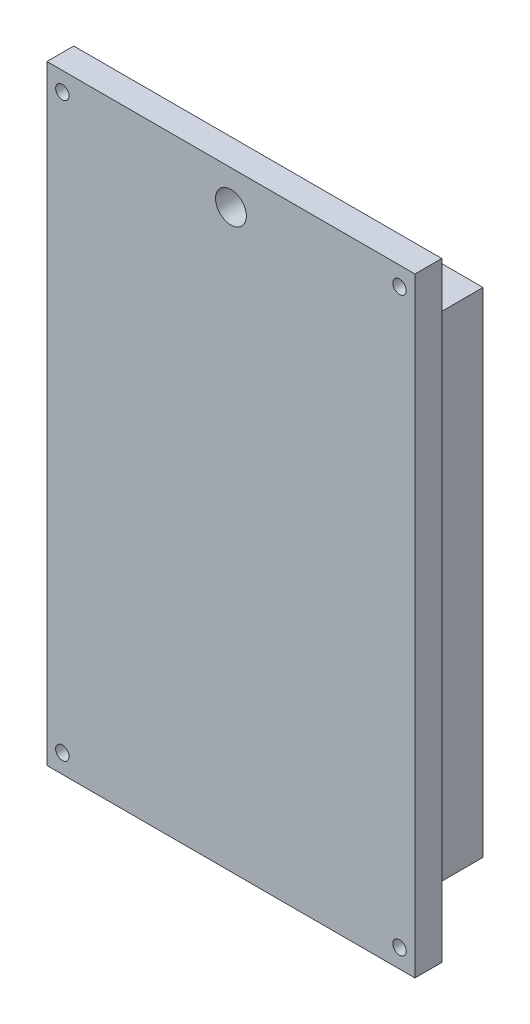
SolidWorks part; units mm, degrees
ref_plane "Front" through (0, 0, 0) normal (0, 0, 1) x (1, 0, 0)
ref_plane "Top" through (0, 0, 0) normal (0, 1, 0) x (1, 0, 0)
ref_plane "Right" through (0, 0, 0) normal (1, 0, 0) x (0, 0, -1)
sketch "arduinoOutline" plane through (0, 0, 0) normal (0, 0, 1) x (1, 0, 0)
  line L0 (0, 32.73) -> (2.54, 35.27) construction
  line L2 (0, 0) -> (0, 32.73) construction
  line L5 (2.54, 35.27) -> (2.54, 36.81) construction
  line L6 (3.54, 37.81) -> (67.6, 37.81) construction
  line L7 (68.6, 36.81) -> (68.6, -14.59) construction
  line L8 (67.6, -15.59) -> (4.06, -15.59) construction
  line L9 (4.06, -15.59) -> (2.54, -14.07) construction
  line L10 (2.54, -14.07) -> (2.54, -2.54) construction
  line L11 (2.54, -2.54) -> (0, 0) construction
  arc A0 (2.54, 36.81) -> (3.54, 37.81) centre (3.54, 36.81) cw construction
  arc A1 (68.6, -14.59) -> (67.6, -15.59) centre (67.6, -14.59) cw construction
  arc A2 (67.6, 37.81) -> (68.6, 36.81) centre (67.6, 36.81) cw construction
  point P8 (2.54, 37.81)
  point P13 (68.6, -15.59)
  point P16 (68.6, 37.81)
  dimension "D6" = 1
  dimension "D9" = 1
  dimension "D10" = 1
  dimension "D1" = 32.73
  dimension "D2" = 135
  dimension "D3" = 3.5921
  dimension "D4" = 2.54
  dimension "D5" = 66.06
  dimension "D7" = 53.4
  dimension "D8" = 64.54
  dimension "D11" = 135
  dimension "D12" = 2.1496
  dimension "D13" = 11.53
  dimension "D14" = 135
  dimension "D15" = 3.5921
sketch "arduinoMountingHolesSketch" plane through (0, 0, 0) normal (0, 0, 1) x (1, 0, 0)
  line L0 (0, 0) -> (0, 32.73) construction
  line L1 (67.6, -15.59) -> (4.06, -15.59) construction
  line L2 (3.54, 37.81) -> (67.6, 37.81) construction
  line L3 (68.6, 36.81) -> (68.6, -14.59) construction
  circle A0 centre (2.54, 2.28) radius 1.25
  circle A1 centre (2.54, 30.45) radius 1.25
  circle A2 centre (54.6, 35.27) radius 1.25
  circle A3 centre (53.35, -13.05) radius 1.25
  dimension "D9" = 2.5
  dimension "D1" = 2.54
  dimension "D2" = 17.87
  dimension "D3" = 2.54
  dimension "D4" = 7.36
  dimension "D5" = 2.54
  dimension "D6" = 14
  dimension "D7" = 2.54
  dimension "D8" = 15.25
sketch "9VbatteryMountingHolesSketch" plane through (0, 0, 0) normal (0, 0, 1) x (1, 0, 0)
  line L0 (0, 16.365) -> (68.6, 16.365) construction
  line L1 (4.875, 40.31) -> (63.725, 40.31) construction
  line L2 (4.875, 40.31) -> (4.875, 88.56) construction
  line L3 (4.875, 88.56) -> (63.725, 88.56) construction
  line L4 (63.725, 40.31) -> (63.725, 88.56) construction
  line L5 (0, 0) -> (0, 32.73) construction
  line L6 (68.6, 36.81) -> (68.6, -14.59) construction
  line L7 (34.3, 40.31) -> (34.3, 88.56) construction
  line L8 (4.875, 64.435) -> (63.725, 64.435) construction
  line L10 (3.54, 37.81) -> (67.6, 37.81) construction
  circle A0 centre (8.625, 86.06) radius 1.25
  circle A1 centre (59.975, 86.06) radius 1.25
  circle A2 centre (8.625, 42.81) radius 1.25
  circle A3 centre (59.975, 42.81) radius 1.25
  point P4 (34.3, 16.365)
  point P5 (34.3, 88.56)
  dimension "D3" = 2.5
  dimension "D1" = 48.25
  dimension "D2" = 58.85
  dimension "D4" = 2.5
  dimension "D5" = 3.75
  dimension "D6" = 2.5
sketch "legBracketMountingHolesSketch" plane through (0, 0, 0) normal (0, 0, 1) x (1, 0, 0)
  line L0 (34.3, 91.06) -> (34.3, 98.06) construction
  line L1 (24.1051, 98.06) -> (44.4949, 98.06) construction
  line L2 (24.1051, 98.06) -> (24.1051, 91.06) construction
  line L3 (24.1051, 91.06) -> (44.4949, 91.06) construction
  line L4 (44.4949, 98.06) -> (44.4949, 91.06) construction
  circle A0 centre (29.2026, 94.56) radius 2
  circle A1 centre (39.3974, 94.56) radius 2
  point P4 (24.1051, 94.56)
  point P5 (34.3, 98.06)
  dimension "D4" = 4
  dimension "D1" = 7
  dimension "D2" = 20.3898
  dimension "D3" = 2.5
  dimension "D5" = 5.0974
sketch "backsideMountingHolesSketch" plane through (0, 0, 0) normal (0, 0, 1) x (1, 0, 0)
  line L0 (0, 41.235) -> (68.6, 41.235) construction
  line L9 (0, 0) -> (0, 32.73) construction
  line L10 (34.3, 40.31) -> (34.3, 88.56) construction
  line L11 (68.6, 36.81) -> (68.6, -14.59) construction
  line L12 (24.1051, 98.06) -> (44.4949, 98.06) construction
  line L13 (4.875, 88.56) -> (63.725, 88.56) construction
  line L14 (4.875, 40.31) -> (4.875, 88.56) construction
  circle A1 centre (2.875, 94.56) radius 1.25
  circle A5 centre (65.725, 94.56) radius 1.25
  circle A6 centre (65.725, -12.09) radius 1.25
  circle A7 centre (2.875, -12.09) radius 1.25
  dimension "D1" = 2.5
  dimension "D2" = 56.825
  dimension "D3" = 6
  dimension "D4" = 2
sketch "Sketch1" plane through (0, 0, 0) normal (0, 0, 1) x (1, 0, 0)
  line L0 (67.6, -15.59) -> (4.06, -15.59) construction
  line L1 (0, 98.06) -> (68.6, 98.06)
  line L2 (0, 98.06) -> (0, -15.59)
  line L3 (0, -15.59) -> (68.6, -15.59)
  line L4 (68.6, 98.06) -> (68.6, -15.59)
  line L5 (0, 0) -> (0, 32.73) construction
  line L6 (68.6, 36.81) -> (68.6, -14.59) construction
  line L9 (24.1051, 98.06) -> (44.4949, 98.06) construction
extrude "bracketBase" add sketch "Sketch1" along normal blind 5
extrude "arduinoMountingHoles" cut sketch "arduinoMountingHolesSketch" against normal through all and the other way blind 22
extrude "9VbatteryMountingHoles" cut sketch "9VbatteryMountingHolesSketch" along normal blind 20
extrude "legBracketMountingHoles" cut sketch "legBracketMountingHolesSketch" along normal blind 13
extrude "backsideMountingHoles" cut sketch "backsideMountingHolesSketch" along normal blind 24
sketch "Sketch2" plane through (0, 0, 5) normal (0, 0, 1) x (1, 0, 0)
  circle A0 centre (53.35, -13.05) radius 1.25 construction
  circle A1 centre (2.54, 2.28) radius 1.25 construction
  circle A2 centre (2.54, 30.45) radius 1.25 construction
  circle A3 centre (54.6, 35.27) radius 1.25 construction
  circle A4 centre (59.975, 42.81) radius 1.25 construction
  circle A5 centre (8.625, 42.81) radius 1.25 construction
  circle A6 centre (59.975, 86.06) radius 1.25 construction
  circle A7 centre (39.3974, 94.56) radius 2 construction
  circle A8 centre (29.2026, 94.56) radius 2 construction
  circle A9 centre (8.625, 86.06) radius 1.25 construction
  circle A10 centre (53.35, -13.05) radius 1.25
  circle A11 centre (2.54, 2.28) radius 1.25
  circle A12 centre (2.54, 30.45) radius 1.25
  circle A13 centre (54.6, 35.27) radius 1.25
  circle A14 centre (59.975, 42.81) radius 1.25
  circle A15 centre (8.625, 42.81) radius 1.25
  circle A16 centre (59.975, 86.06) radius 1.25
  circle A17 centre (39.3974, 94.56) radius 2
  circle A18 centre (29.2026, 94.56) radius 2
  circle A19 centre (8.625, 86.06) radius 1.25
extrude "cover" add sketch "Sketch2" against normal up to surface (5 mm away) up to face at (1.625, -12.09, 0)
sketch "Sketch3" plane through (0, 0, 5) normal (0, 0, 1) x (1, 0, 0)
  line L1 (68.6, 98.06) -> (0, 98.06) construction
  line L2 (0, 98.06) -> (0, -15.59) construction
  line L3 (2.3, -4.765) -> (2.3, 87.235)
  line L4 (5.3, -1.765) -> (63.3, -1.765)
  line L5 (5.3, -1.765) -> (5.3, 84.235)
  line L6 (5.3, 84.235) -> (63.3, 84.235)
  line L7 (63.3, -1.765) -> (63.3, 84.235)
  line L8 (5.3, -1.765) -> (63.3, 84.235) construction
  line L9 (5.3, 84.235) -> (63.3, -1.765) construction
  line L10 (2.3, 87.235) -> (66.3, 87.235)
  line L11 (66.3, -4.765) -> (66.3, 87.235)
  line L12 (2.3, -4.765) -> (66.3, -4.765)
  point P4 (34.3, 98.06)
  point P5 (0, 41.235)
  point P6 (34.3, 41.235)
  dimension "D1" = 86
  dimension "D2" = 58
  dimension "D3" = 3
extrude "breadBoardCavity" add sketch "Sketch3" along normal blind 10
ref_plane "Plane1" through (0, 0, 2.5) normal (0, 0, 1) x (1, 0, 0)
mirror "Mirror1" about plane through (0, 0, 2.5) normal (0, 0, 1) of "breadBoardCavity"
sketch "Sketch4" plane through (0, 87.235, 0) normal (0, 1, 0) x (1, 0, 0)
  line L4 (66.3, -5) -> (2.3, -5)
  line L5 (2.3, -5) -> (2.3, -15)
  line L6 (2.3, -15) -> (66.3, -15)
  line L7 (66.3, -15) -> (66.3, -5)
  line L8 (66.3, -5) -> (2.3, -5)
  line L9 (2.3, -5) -> (2.3, -15)
  line L10 (2.3, -15) -> (66.3, -15)
  line L11 (66.3, -15) -> (66.3, -5)
  dimension "D1" = 0
extrude "Cut-Extrude1" cut sketch "Sketch4" against normal through all
sketch "Sketch5" plane through (0, 0, 0) normal (0, 0, -1) x (-1, 0, 0)
  line L1 (-68.6, 98.06) -> (0, 98.06) construction
  circle A0 centre (-34.3, 91.685) radius 2.875
  point P2 (-34.3, 98.06)
  point P8 (0, 0)
  point P9 (-34.3, 94.56)
  point P10 (-35.5805, 94.56)
  dimension "D1" = 5.75
  dimension "D2" = 3.5
extrude "toggleSwitchHole" cut sketch "Sketch5" against normal blind 10
equation "\"D2@backsideMountingHolesSketch\"=113.65mm/2"
